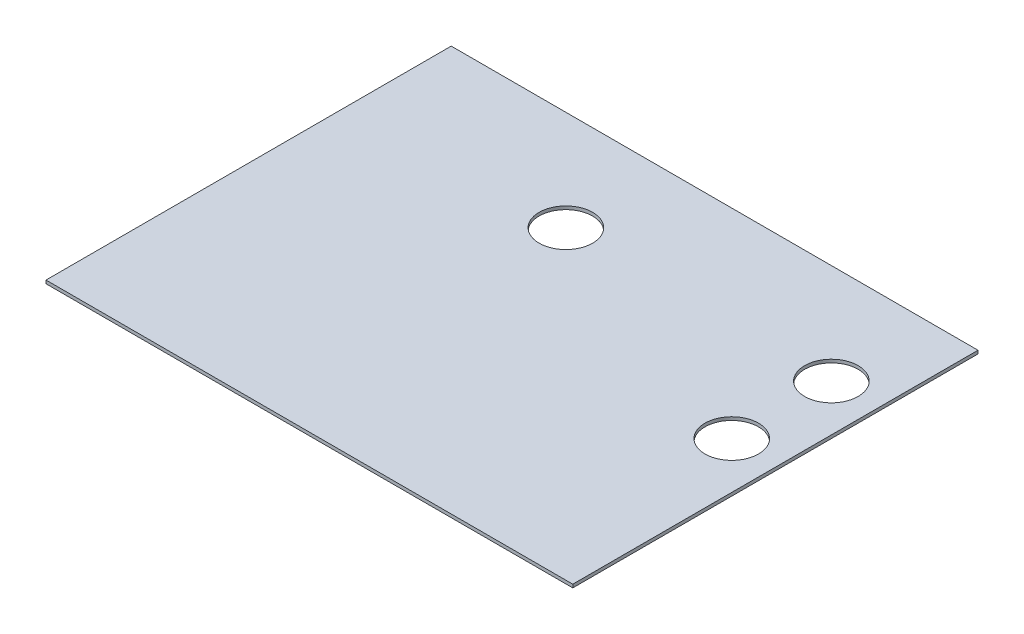
SolidWorks part; units mm, degrees
ref_plane "Front Plane" through (0, 0, 0) normal (0, 0, 1) x (1, 0, 0)
ref_plane "Top Plane" through (0, 0, 0) normal (0, 1, 0) x (1, 0, 0)
ref_plane "Right Plane" through (0, 0, 0) normal (1, 0, 0) x (0, 0, -1)
sketch "Sketch1" plane through (0, 0, 0) normal (0, 1, 0) x (1, 0, 0)
  line L1 (-162.5, 125) -> (162.5, 125)
  line L2 (-162.5, 125) -> (-162.5, -125)
  line L3 (-162.5, -125) -> (162.5, -125)
  line L4 (162.5, 125) -> (162.5, -125)
  line L5 (-162.5, 125) -> (162.5, -125) construction
  line L6 (-162.5, -125) -> (162.5, 125) construction
  point P0 (0, 0)
  dimension "D1" = 250
  dimension "D2" = 325
extrude "Boss-Extrude1" add sketch "Sketch1" along normal blind 2
sketch "Sketch2" plane through (0, 2, 0) normal (0, 1, 0) x (1, 0, 0)
  line L0 (133.7364, 1.8436) -> (133.7364, 69.3545) construction
  line L1 (133.7364, 63.3119) -> (-92.8225, 63.3119) construction
  line L2 (-30.0735, 69.0356) -> (-30.0735, 32.7247) construction
  circle A0 centre (133.7364, 1.8436) radius 16.5
  circle A1 centre (133.7364, 63.3119) radius 16.5
  circle A2 centre (-30.0735, 63.3119) radius 16.5
  dimension "D1" = 33
  dimension "D2" = 33
  dimension "D3" = 33
extrude "Cut-Extrude1" cut sketch "Sketch2" against normal up to next
